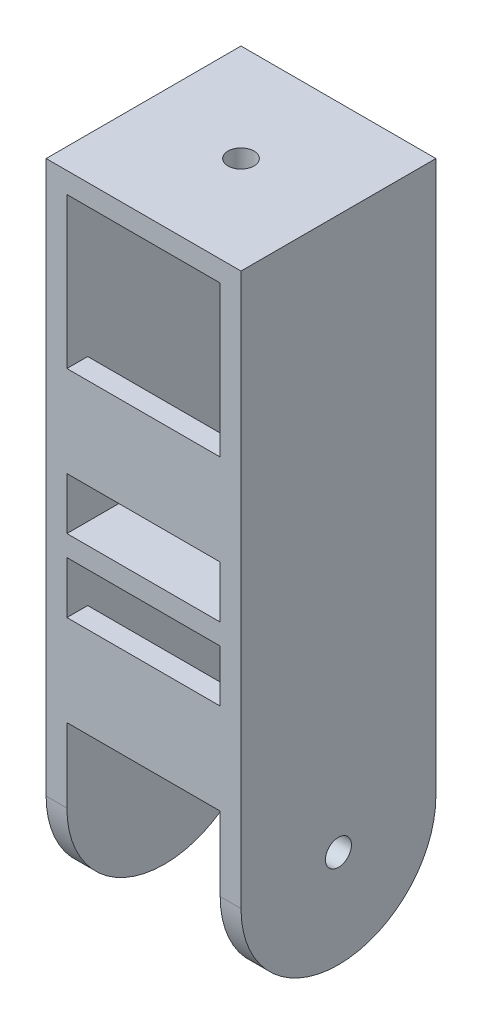
SolidWorks part; units mm, degrees
ref_plane "Front Plane" through (0, 0, 0) normal (0, 0, 1) x (1, 0, 0)
ref_plane "Top Plane" through (0, 0, 0) normal (0, 1, 0) x (1, 0, 0)
ref_plane "Right Plane" through (0, 0, 0) normal (1, 0, 0) x (0, 0, -1)
sketch "Sketch1" plane through (0, 0, 0) normal (0, 0, 1) x (1, 0, 0)
  line L0 (8, -8) -> (8, -250)
  line L1 (0, 0) -> (8, 0)
  line L2 (0, 0) -> (0, -250)
  line L3 (0, -250) -> (8, -250)
  line L4 (75, 0) -> (75, -250)
  line L5 (67, -8) -> (67, -250)
  line L6 (67, 0) -> (75, 0)
  line L7 (67, -250) -> (75, -250)
  line L10 (8, -117) -> (8, -125)
  line L12 (67, -117) -> (67, -129)
  line L13 (8, -121) -> (67, -121)
  line L14 (8, -121) -> (8, -129)
  line L15 (8, -129) -> (67, -129)
  line L16 (67, -121) -> (67, -129)
  line L17 (75, 0) -> (0, 0)
  line L18 (75, 0) -> (75, -8)
  line L19 (67, -8) -> (8, -8)
  line L20 (0, 0) -> (0, -8)
  dimension "D1" = 75
  dimension "D2" = 250
  dimension "D3" = 8
  dimension "D4" = 8
  dimension "D5" = 8
  dimension "D6" = 121
  dimension "D7" = 8
extrude "Boss-Extrude2" add sketch "Sketch1" along normal blind 75 contours L0 L15 L5 L12 L13 L10 | L5 L12 L7 L4 L6 | L2 L3 L0 L10 L1 region at (5.3899, -62.5, 0) region at (37.5, -125, 0)
fillet "Fillet1" radius 37.5 4 edges at (4, -250, 0) (71, -250, 0) (71, -250, 75) (4, -250, 75)
sketch "Sketch2" plane through (75, 0, 0) normal (1, 0, 0) x (0, 0, -1)
  circle A0 centre (-37.5, -212.5) radius 5
extrude "Cut-Extrude1" cut sketch "Sketch2" against normal blind 10
sketch "Sketch3" plane through (67, 0, 0) normal (-1, 0, 0) x (0, 0, 1)
  circle A0 centre (37.5, -212.5) radius 5
  circle A1 centre (37.5, -212.5) radius 15
extrude "Boss-Extrude3" add sketch "Sketch3" along normal blind 7.5
sketch "Sketch4" plane through (59.5, 0, 0) normal (-1, 0, 0) x (0, 0, 1)
  circle A0 centre (37.5, -212.5) radius 5
  circle A1 centre (37.5, -212.5) radius 10
extrude "Boss-Extrude4" add sketch "Sketch4" along normal blind 7.5
sketch "Sketch5" plane through (0, 0, 0) normal (0, 1, 0) x (1, 0, 0)
  line L0 (75, -75) -> (75, 0) construction
  line L2 (0, -75) -> (75, -75) construction
  circle A0 centre (37.5, -37.5) radius 5
  dimension "D1" = 37.5
  dimension "D2" = 37.5
extrude "Cut-Extrude2" cut sketch "Sketch5" against normal blind 10
sketch "Sketch6" plane through (0, 0, 0) normal (0, 0, -1) x (-1, 0, 0)
  line L0 (-75, 0) -> (-75, -212.5) construction
  line L1 (-75, -66) -> (0, -66)
  line L2 (-75, -66) -> (-75, -101)
  line L3 (-75, -101) -> (0, -101)
  line L4 (0, -66) -> (0, -101)
  line L5 (0, 0) -> (0, -212.5) construction
  line L6 (-8, -129) -> (-67, -129) construction
  line L7 (-75, -149) -> (0, -149)
  line L8 (-75, -149) -> (-75, -184)
  line L9 (-75, -184) -> (0, -184)
  line L10 (0, -149) -> (0, -184)
  line L11 (-8, -121) -> (-67, -121) construction
  dimension "D1" = 35
  dimension "D2" = 35
  dimension "D3" = 20
  dimension "D4" = 20
extrude "Boss-Extrude5" add sketch "Sketch6" against normal blind 8
sketch "Sketch7" plane through (0, 0, 75) normal (0, 0, 1) x (1, 0, 0)
  line L1 (8, -66) -> (67, -66)
  line L2 (8, -66) -> (8, -101)
  line L3 (8, -101) -> (67, -101)
  line L4 (67, -66) -> (67, -101)
  line L5 (8, -149) -> (67, -149)
  line L6 (8, -149) -> (8, -184)
  line L7 (8, -184) -> (67, -184)
  line L8 (67, -149) -> (67, -184)
extrude "Boss-Extrude6" add sketch "Sketch7" against normal blind 8
